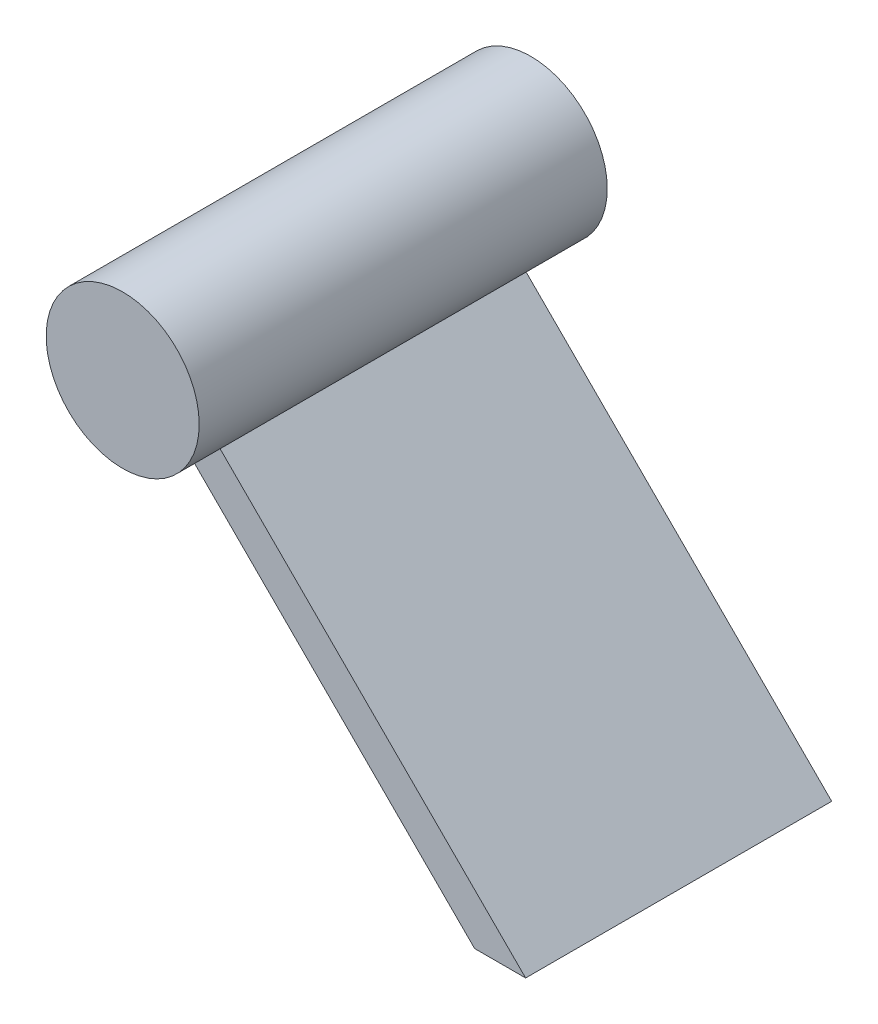
SolidWorks part; units mm, degrees
note: The reader was unsure of these and kept them because the rebuilt part matched: shared geometry of "Sketch3<3>".
ref_plane "Front Plane" through (0, 0, 0) normal (0, 0, 1) x (1, 0, 0)
ref_plane "Top Plane" through (0, 0, 0) normal (0, 1, 0) x (1, 0, 0)
ref_plane "Right Plane" through (0, 0, 0) normal (1, 0, 0) x (0, 0, -1)
sketch "Sketch3" plane through (0, 0, 0) normal (0, 0, 1) x (1, 0, 0)
  line L0 (-34.7968, 0) -> (143.8268, 0) construction
  line L1 (-17.3388, -30) -> (179.8432, -30) construction
  line L2 (0, 0) -> (30, -30)
  line L3 (30, -30) -> (35, -30)
  line L4 (35, -30) -> (5, 0)
  line L5 (5, 0) -> (0, 0)
  circle A0 centre (0.5, 6) radius 7.5
  dimension "D3" = 15
  dimension "D1" = 45
  dimension "D2" = 30
  dimension "D4" = 5
  dimension "D5" = 6
extrude "Boss-Extrude2" add sketch "Sketch3" along normal mid plane 30 contours L5 A0 L2 | A0 L2 L3 L4
extrude "Boss-Extrude3" add sketch "Sketch3<3>" along normal mid plane 40 contours A0
sketch "Sketch3<3>" plane through (0, 0, 0) normal (0, 0, 1) x (1, 0, 0) same geometry as "Sketch3"
